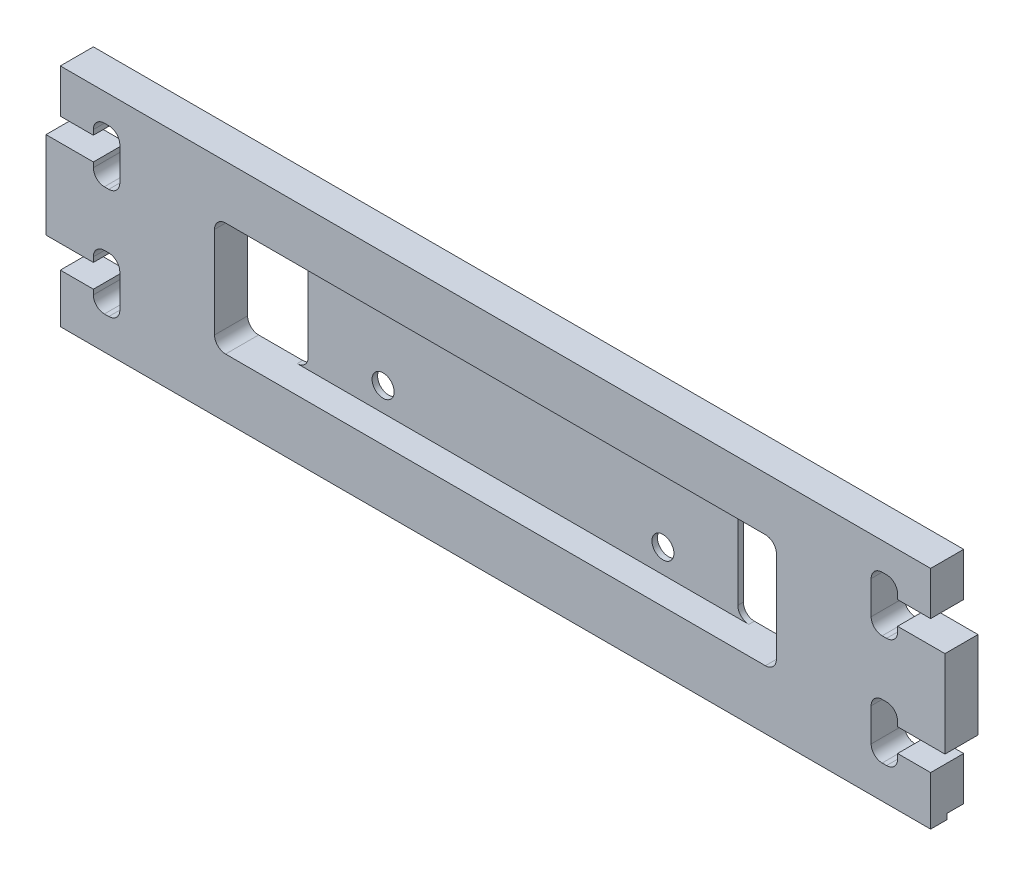
SolidWorks part; units mm, degrees
ref_plane "Front Plane" through (0, 0, 0) normal (0, 0, 1) x (1, 0, 0)
ref_plane "Top Plane" through (0, 0, 0) normal (0, 1, 0) x (1, 0, 0)
ref_plane "Right Plane" through (0, 0, 0) normal (1, 0, 0) x (0, 0, -1)
sketch "Sketch1" plane through (0, 0, 0) normal (0, 0, 1) x (1, 0, 0)
  line L0 (-39.5, 0) -> (39.5, 0) construction
  line L1 (-39.5, 10) -> (39.5, 10)
  line L2 (-39.5, 10) -> (-39.5, -10)
  line L3 (-39.5, -10) -> (39.5, -10)
  line L4 (39.5, 10) -> (39.5, -10)
  line L5 (-39.5, 10) -> (39.5, -10) construction
  line L6 (-39.5, -10) -> (39.5, 10) construction
  line L7 (0, 10) -> (0, -10) construction
  line L9 (-40.8, -3.95) -> (-39.5, -3.95)
  line L10 (-40.8, -3.95) -> (-40.8, 3.95)
  line L11 (-40.8, 3.95) -> (-39.5, 3.95)
  line L12 (-39.5, -3.95) -> (-39.5, 3.95)
  line L13 (-40.8, -3.95) -> (-39.5, 3.95) construction
  line L14 (-40.8, 3.95) -> (-39.5, -3.95) construction
  line L16 (40.8, 3.95) -> (39.5, 3.95)
  line L17 (40.8, -3.95) -> (40.8, 3.95)
  line L18 (40.8, -3.95) -> (39.5, -3.95)
  line L19 (-39.5, 5) -> (39.5, 5) construction
  line L20 (-35.3, 7.5) -> (-35.3, 2.5) construction
  line L21 (-36.5, 3.95) -> (-39.5, 3.95)
  line L22 (-36.5, 3.95) -> (-36.5, 6.05)
  line L23 (-36.5, 6.05) -> (-39.5, 6.05)
  line L24 (-39.5, 3.95) -> (-39.5, 6.05)
  line L25 (-36.5, 3.95) -> (-39.5, 6.05) construction
  line L26 (-36.5, 6.05) -> (-39.5, 3.95) construction
  line L27 (-34.1, 7.5) -> (-36.5, 7.5)
  line L28 (-34.1, 7.5) -> (-34.1, 2.5)
  line L29 (-34.1, 2.5) -> (-36.5, 2.5)
  line L30 (-36.5, 7.5) -> (-36.5, 2.5)
  line L31 (-34.1, 7.5) -> (-36.5, 2.5) construction
  line L32 (-34.1, 2.5) -> (-36.5, 7.5) construction
  line L33 (-34.1, -7.5) -> (-36.5, -7.5)
  line L34 (-34.1, -7.5) -> (-34.1, -2.5)
  line L35 (-34.1, -2.5) -> (-36.5, -2.5)
  line L36 (-36.5, -7.5) -> (-36.5, -2.5)
  line L37 (-36.5, -3.95) -> (-39.5, -3.95)
  line L38 (-36.5, -6.05) -> (-39.5, -6.05)
  line L39 (36.5, 3.95) -> (39.5, 3.95)
  line L40 (36.5, 6.05) -> (39.5, 6.05)
  line L41 (36.5, 7.5) -> (36.5, 2.5)
  line L42 (34.1, 7.5) -> (36.5, 7.5)
  line L43 (34.1, 7.5) -> (34.1, 2.5)
  line L44 (34.1, 2.5) -> (36.5, 2.5)
  line L45 (34.1, -2.5) -> (36.5, -2.5)
  line L46 (34.1, -7.5) -> (34.1, -2.5)
  line L47 (34.1, -7.5) -> (36.5, -7.5)
  line L48 (36.5, -7.5) -> (36.5, -2.5)
  line L49 (36.5, -6.05) -> (39.5, -6.05)
  line L50 (36.5, -3.95) -> (39.5, -3.95)
  point P0 (0, 0)
  point P10 (-40.15, 0)
  point P15 (-38, 5)
  point P35 (-35.3, 5)
  dimension "D1" = 79
  dimension "D2" = 20
  dimension "D4" = 1.3
  dimension "D7" = 5
  dimension "D8" = 2.1
  dimension "D9" = 3
  dimension "D10" = 2.4
  dimension "D11" = 5
extrude "Base shape" add sketch "Sketch1" along normal blind 3 contours L4 L1 L2 L3 | L9 L2 L11 L10 | L16 L4 L18 L17 region at (0, 0, 0) region at (-40.15, 0, 0) region at (40.15, 0, 0)
sketch "Sketch4" plane through (0, -10, 0) normal (0, -1, 0) x (1, 0, 0)
  line L0 (39.5, 3) -> (39.5, 0) construction
  line L1 (-39.5, 3) -> (39.5, 3)
  line L2 (-39.5, 3) -> (-39.5, 1.5)
  line L3 (-39.5, 1.5) -> (39.5, 1.5)
  line L4 (39.5, 3) -> (39.5, 1.5)
extrude "Floor lip" add sketch "Sketch4" along normal blind 0.5
sketch "Sketch6" plane through (0, 0, 0) normal (0, 0, -1) x (-1, 0, 0)
  line L0 (0, 0) -> (0, -10) construction
  line L1 (39.5, -10) -> (-39.5, -10) construction
  line L2 (-4, -10) -> (4, -10) construction
  line L3 (39.5, -10) -> (-39.5, -10) construction
  line L4 (-4, -9) -> (4, -9)
  line L5 (-4, -11) -> (4, -11)
  arc A0 (-4, -9) -> (-4, -11) centre (-4, -10) ccw
  arc A1 (4, -11) -> (4, -9) centre (4, -10) ccw
  point P9 (0, -10)
  dimension "D1" = 2
  dimension "D2" = 8
extrude "Nail cutout" cut sketch "Sketch6" against normal up to surface (1.5 mm away) up to face at (0, -10.25, 1.5)
sketch "Sketch3" plane through (-40.8, 0, 0) normal (-1, 0, 0) x (0, 0, 1)
  line L0 (0, 6.05) -> (3, 3.95) construction
  line L1 (0, 6.05) -> (3, 6.05)
  line L2 (0, 6.05) -> (0, 3.95)
  line L3 (0, 3.95) -> (3, 3.95)
  line L4 (3, 6.05) -> (3, 3.95)
  line L5 (0, -3.95) -> (3, -6.05) construction
  line L6 (0, -3.95) -> (3, -3.95)
  line L7 (0, -3.95) -> (0, -6.05)
  line L8 (0, -6.05) -> (3, -6.05)
  line L9 (3, -3.95) -> (3, -6.05)
  point P6 (1.5, 5)
  point P13 (1.5, -5)
ref_axis "Tap axis top" through (-53.7846, 5, 1.5) along (1, 0, 0)
ref_axis "Tap axis bottom" through (-54.2844, -5, 1.5) along (1, 0, 0)
fillet "Mill fillets" radius 1 16 edges at (36.5, -7.5, 1.5) (36.5, 2.5, 1.5) (34.1, 2.5, 1.5) (34.1, -7.5, 1.5) (36.5, -2.5, 1.5) (36.5, 7.5, 1.5) (34.1, -2.5, 1.5) (34.1, 7.5, 1.5) (-36.5, -2.5, 1.5) (-34.1, -2.5, 1.5) (-34.1, -7.5, 1.5) (-36.5, -7.5, 1.5) (-36.5, 2.5, 1.5) (-34.1, 2.5, 1.5) (-34.1, 7.5, 1.5) (-36.5, 7.5, 1.5)
sketch "Sketch8" plane through (0, 0, 3) normal (0, 0, 1) x (1, 0, 0)
  line L0 (-40.8, 0) -> (40.8, 0) construction
  line L1 (-40.8, -3.95) -> (-40.8, 3.95) construction
  line L2 (40.8, -3.95) -> (40.8, 3.95) construction
  line L4 (-24.5, 5.15) -> (24.5, 5.15)
  line L5 (-25.5, 4.15) -> (-25.5, -4.15)
  line L6 (-24.5, -5.15) -> (24.5, -5.15)
  line L7 (25.5, 4.15) -> (25.5, -4.15)
  line L8 (-25.5, 5.15) -> (25.5, -5.15) construction
  line L9 (-25.5, -5.15) -> (25.5, 5.15) construction
  arc A0 (24.5, -5.15) -> (25.5, -4.15) centre (24.5, -4.15) ccw
  arc A1 (24.5, 5.15) -> (25.5, 4.15) centre (24.5, 4.15) cw
  arc A2 (-25.5, -4.15) -> (-24.5, -5.15) centre (-24.5, -4.15) ccw
  arc A3 (-24.5, 5.15) -> (-25.5, 4.15) centre (-24.5, 4.15) ccw
  point P6 (0, 0)
  dimension "D3" = 1
  dimension "D1" = 51
  dimension "D2" = 10.3
extrude "Led strip pocket" cut sketch "Sketch8" against normal offset from surface (2.5 mm away) 0.5 up to face at (0, -0.6712, 0)
sketch "Sketch9" plane through (0, 0, 0.5) normal (0, 0, 1) x (1, 0, 0)
  line L0 (-19.5, 5.15) -> (-19.5, -5.15)
  line L1 (0, 5.15) -> (0, -5.15) construction
  line L2 (19.5, 5.15) -> (19.5, -5.15)
  line L3 (-25.5, -2.978) -> (25.5, -2.978) construction
  line L4 (25.5, -4.15) -> (25.5, 4.15)
  line L5 (24.5, 5.15) -> (-24.5, 5.15)
  line L6 (-25.5, 4.15) -> (-25.5, -4.15)
  line L7 (-24.5, -5.15) -> (24.5, -5.15)
  line L8 (25.5, -4.15) -> (25.5, 4.15)
  line L9 (24.5, 5.15) -> (-24.5, 5.15)
  line L10 (-25.5, 4.15) -> (-25.5, -4.15)
  line L11 (-24.5, -5.15) -> (24.5, -5.15)
  circle A0 centre (-12.7, -2.978) radius 1
  circle A1 centre (12.7, -2.978) radius 1
  arc A4 (24.5, -5.15) -> (25.5, -4.15) centre (24.5, -4.15) ccw
  arc A5 (25.5, 4.15) -> (24.5, 5.15) centre (24.5, 4.15) ccw
  arc A6 (-24.5, 5.15) -> (-25.5, 4.15) centre (-24.5, 4.15) ccw
  arc A7 (-25.5, -4.15) -> (-24.5, -5.15) centre (-24.5, -4.15) ccw
  arc A8 (24.5, -5.15) -> (25.5, -4.15) centre (24.5, -4.15) ccw
  arc A9 (25.5, 4.15) -> (24.5, 5.15) centre (24.5, 4.15) ccw
  arc A10 (-24.5, 5.15) -> (-25.5, 4.15) centre (-24.5, 4.15) ccw
  arc A11 (-25.5, -4.15) -> (-24.5, -5.15) centre (-24.5, -4.15) ccw
  arc M13 (24.5, -5.15) -> (25.5, -4.15) centre (24.5, -4.15) ccw
  line M14 (25.5, -4.15) -> (25.5, 4.15)
  arc M15 (25.5, 4.15) -> (24.5, 5.15) centre (24.5, 4.15) ccw
  line M16 (24.5, 5.15) -> (-24.5, 5.15)
  arc M17 (-24.5, 5.15) -> (-25.5, 4.15) centre (-24.5, 4.15) ccw
  line M18 (-25.5, 4.15) -> (-25.5, -4.15)
  arc M19 (-25.5, -4.15) -> (-24.5, -5.15) centre (-24.5, -4.15) ccw
  line M20 (-24.5, -5.15) -> (24.5, -5.15)
  dimension "D4" = 2
  dimension "D2" = 6
  dimension "D3" = 8.128
  dimension "D5" = 25.4
  dimension "D1" = 0
extrude "Led strip cuts" cut sketch "Sketch9" against normal up to next contours L0 M16 M17 M18 M19 M20 | L2 M16 M20 M13 M14 M15 | A0 | A1 region at (-22.4806, 0, 0.5) region at (22.4806, 0, 0.5)
fillet "Led strip cut fillets" radius 1 4 edges at (19.5, -5.15, 0.25) (19.5, 5.15, 0.25) (-19.5, -5.15, 0.25) (-19.5, 5.15, 0.25)
